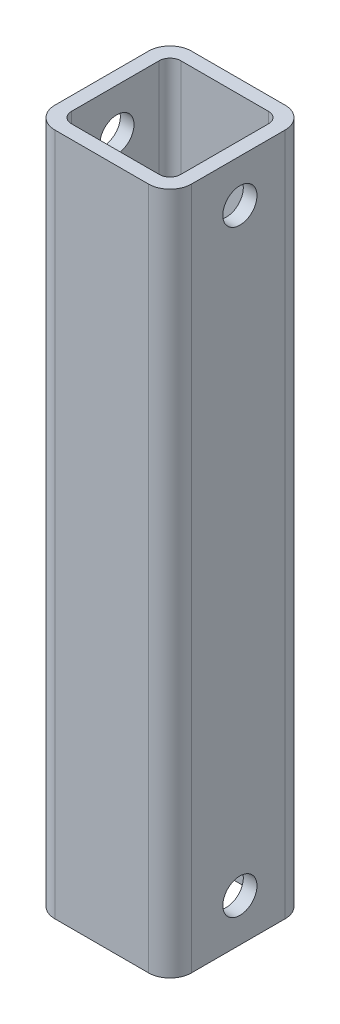
SolidWorks part; units mm, degrees
ref_plane "Front Plane" through (0, 0, 0) normal (0, 0, 1) x (1, 0, 0)
ref_plane "Top Plane" through (0, 0, 0) normal (0, 1, 0) x (1, 0, 0)
ref_plane "Right Plane" through (0, 0, 0) normal (1, 0, 0) x (0, 0, -1)
sketch "Sketch1" plane through (0, 0, 0) normal (0, 1, 0) x (1, 0, 0)
  line L1 (4, 0) -> (21.4, 0)
  line L2 (0, 4) -> (0, 21.4)
  line L3 (4, 25.4) -> (21.4, 25.4)
  line L4 (25.4, 4) -> (25.4, 21.4)
  line L6 (20.86, 2.54) -> (4.54, 2.54)
  line L7 (22.86, 4.54) -> (22.86, 20.86)
  line L8 (2.54, 4.54) -> (2.54, 20.86)
  line L9 (20.86, 22.86) -> (4.54, 22.86)
  line L10 (22.86, 2.54) -> (2.54, 22.86) construction
  line L11 (2.54, 2.54) -> (22.86, 22.86) construction
  arc A0 (2.54, 20.86) -> (4.54, 22.86) centre (4.54, 20.86) cw
  arc A1 (22.86, 20.86) -> (20.86, 22.86) centre (20.86, 20.86) ccw
  arc A2 (22.86, 4.54) -> (20.86, 2.54) centre (20.86, 4.54) cw
  arc A3 (4.54, 2.54) -> (2.54, 4.54) centre (4.54, 4.54) cw
  arc A4 (0, 21.4) -> (4, 25.4) centre (4, 21.4) cw
  arc A5 (21.4, 25.4) -> (25.4, 21.4) centre (21.4, 21.4) cw
  arc A6 (21.4, 0) -> (25.4, 4) centre (21.4, 4) ccw
  arc A7 (4, 0) -> (0, 4) centre (4, 4) cw
  point P9 (12.7, 12.7)
  point P31 (0, 0)
  dimension "D1" = 2
  dimension "D2" = 2
  dimension "D3" = 4
  dimension "D4" = 4
  dimension "D5" = 4
  dimension "D6" = 4
extrude "Boss-Extrude1" add sketch "Sketch1" along normal blind 127
sketch "Sketch2" plane through (0, 0, 0) normal (1, 0, 0) x (0, 0, -1)
  circle A0 centre (12.9921, 7.9375) radius 3.175
  circle A1 centre (12.9921, 119.0625) radius 3.175
extrude "Cut-Extrude1" cut sketch "Sketch2" along normal up to surface (25.4 mm away) up to face at (25.4, 63.5, -12.7)
